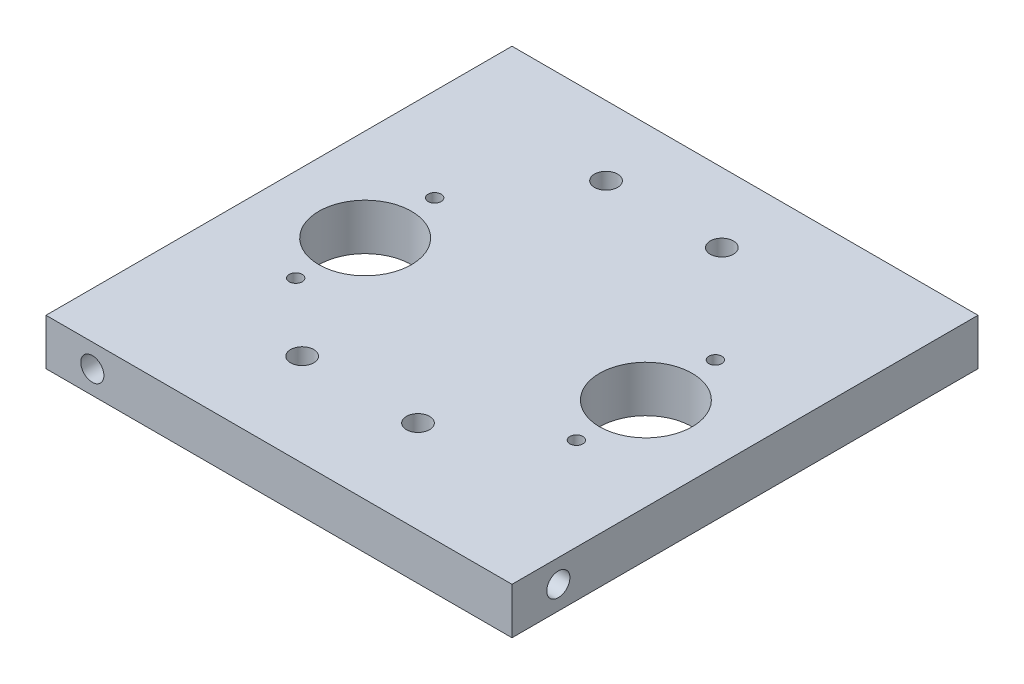
SolidWorks part; units mm, degrees
material "6061 Alloy"
ref_plane "Front" through (0, 0, 0) normal (0, 0, 1) x (1, 0, 0)
ref_plane "Top" through (0, 0, 0) normal (0, 1, 0) x (1, 0, 0)
ref_plane "Right" through (0, 0, 0) normal (1, 0, 0) x (0, 0, -1)
sketch "Sketch1" plane through (0, 0, 0) normal (0, 1, 0) x (1, 0, 0)
  line L1 (0, 0) -> (127.762, 0)
  line L2 (0, 0) -> (0, 127.762)
  line L3 (0, 127.762) -> (127.762, 127.762)
  line L4 (127.762, 0) -> (127.762, 127.762)
  dimension "D1" = 127.762
  dimension "D2" = 127.762
extrude "Main Plate" add sketch "Sketch1" along normal blind 12.7
sketch "Sketch2" plane through (0, 12.7, 0) normal (0, 1, 0) x (1, 0, 0)
  line L0 (0, 127.762) -> (0, 0) construction
  line L1 (127.762, 127.762) -> (0, 127.762) construction
  circle A0 centre (44.831, 108.712) radius 3.175
  dimension "D1" = 6.35
  dimension "D2" = 44.831
  dimension "D3" = 19.05
extrude "U-Bolt Hole" cut sketch "Sketch2" against normal blind 12.7
pattern_linear "U-Bolt Pattern" count 2 spacing 31.75 along (1, 0, 0) count 2 spacing 83.312 along (0, 0, 1) of "U-Bolt Hole"
sketch "Sketch3" plane through (0, 12.7, 0) normal (0, 1, 0) x (1, 0, 0)
  line L0 (0, 127.762) -> (0, 0) construction
  line L1 (0, 0) -> (127.762, 0) construction
  circle A0 centre (25.4, 43.053) radius 1.778
  dimension "D1" = 3.556
  dimension "D2" = 25.4
  dimension "D3" = 43.053
extrude "Raptor Bolt Hole" cut sketch "Sketch3" against normal blind 12.7
pattern_linear "Raptor Bolt Pattern" count 2 spacing 38.1 along (0, 0, -1) count 2 spacing 76.962 along (1, 0, 0) of "Raptor Bolt Hole"
sketch "Sketch4" plane through (0, 12.7, 0) normal (0, 1, 0) x (1, 0, 0)
  line L0 (0, 127.762) -> (0, 0) construction
  circle A0 centre (25.4, 62.103) radius 12.7
  point P2 (0, 0)
  dimension "D1" = 25.4
  dimension "D2" = 19.05
  dimension "D3" = 25.4
extrude "Co2 Cylinder Hole" cut sketch "Sketch4" against normal blind 12.7
pattern_linear "Co2 Pattern" count 2 spacing 76.962 along (1, 0, 0) of "Co2 Cylinder Hole"
sketch "Sketch5" plane through (0, 0, 0) normal (0, 0, 1) x (1, 0, 0)
  line L0 (0, 12.7) -> (0, 0) construction
  line L1 (0, 0) -> (127.762, 0) construction
  circle A0 centre (12.7, 6.3103) radius 3.175
  dimension "D1" = 6.35
  dimension "D2" = 12.7
  dimension "D3" = 6.3103
extrude "Frame attachment hole 1" cut sketch "Sketch5" against normal blind 12.7
sketch "Sketch6" plane through (0, 0, 0) normal (-1, 0, 0) x (0, 0, 1)
  line L2 (-127.762, 0) -> (0, 0) construction
  line L3 (-127.762, 12.7) -> (-127.762, 0) construction
  circle A0 centre (-115.062, 6.35) radius 3.175
  dimension "D1" = 6.35
  dimension "D2" = 6.35
  dimension "D3" = 12.7
extrude "Frame attachment hole 2" cut sketch "Sketch6" against normal blind 12.7
sketch "Sketch7" plane through (0, 0, -127.762) normal (0, 0, -1) x (-1, 0, 0)
  line L2 (-127.762, 0) -> (0, 0) construction
  line L3 (-127.762, 12.7) -> (-127.762, 0) construction
  circle A0 centre (-115.062, 6.35) radius 3.175
  dimension "D1" = 6.35
  dimension "D2" = 6.35
  dimension "D3" = 12.7
extrude "Frame attachment hole 3" cut sketch "Sketch7" against normal blind 12.7
sketch "Sketch8" plane through (127.762, 0, 0) normal (1, 0, 0) x (0, 0, -1)
  line L2 (0, 0) -> (127.762, 0) construction
  line L3 (0, 12.7) -> (0, 0) construction
  circle A0 centre (12.7, 6.35) radius 3.175
  dimension "D1" = 6.35
  dimension "D2" = 6.35
  dimension "D3" = 12.7
extrude "Frame attachment hole 4" cut sketch "Sketch8" against normal blind 12.7
